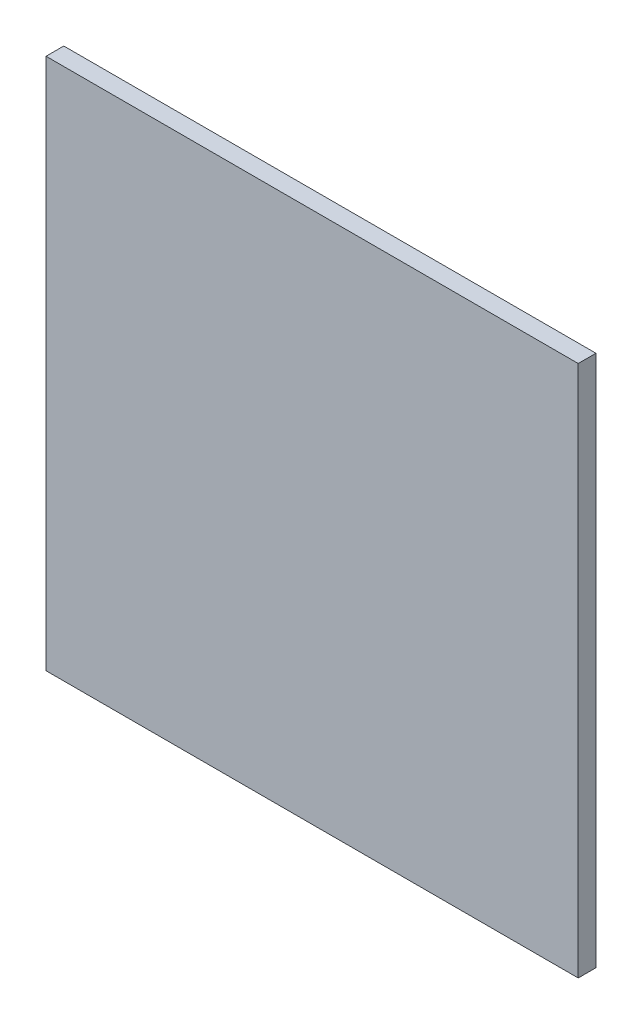
SolidWorks part; units mm, degrees
ref_plane "Спереди" through (0, 0, 0) normal (0, 0, 1) x (1, 0, 0)
ref_plane "Сверху" through (0, 0, 0) normal (0, 1, 0) x (1, 0, 0)
ref_plane "Справа" through (0, 0, 0) normal (1, 0, 0) x (0, 0, -1)
sketch "Эскиз1" plane through (0, 0, 0) normal (0, 0, 1) x (1, 0, 0)
  line L5 (30, 30) -> (-30, 30)
  line L6 (30, 30) -> (30, -30)
  line L7 (30, -30) -> (-30, -30)
  line L8 (-30, 30) -> (-30, -30)
  line L9 (30, 30) -> (-30, -30) construction
  line L10 (30, -30) -> (-30, 30) construction
  point P0 (0, 0)
  point P1 (0, 0)
extrude "Бобышка-Вытянуть1" add sketch "Эскиз1" along normal blind 2
sketch "Острова" plane through (0, 0, 2) normal (0, 0, 1) x (1, 0, 0)
  circle A0 centre (0, 0) radius 3.4
  circle A27 centre (-14.6858, 0.6384) radius 0.5
sketch "Внешний контур" plane through (0, 0, 2) normal (0, 0, 1) x (1, 0, 0)
  circle A0 centre (0, 0) radius 18.1
sketch "малое" plane through (0, 0, 2) normal (0, 0, 1) x (1, 0, 0)
  circle A0 centre (-14.6858, 0.6384) radius 3.1837
sketch "Платина" plane through (0, 0, 2) normal (0, 0, 1) x (1, 0, 0)
  line L0 (-16.46, -2.2319) -> (-17.6833, -3.1445)
  line L1 (-15.9169, 4.5359) -> (-17.3141, 3.4937)
  line L2 (-9.9961, -0.621) -> (-8.9843, -0.8481)
  line L3 (-8.1465, 12.0191) -> (-11.9685, 4.612)
  circle A0 centre (15.8604, -7.3958) radius 0.3
  circle A1 centre (-15.8604, -7.3958) radius 0.3
  circle A2 centre (-15.1554, -8.75) radius 0.2
  circle A3 centre (15.1554, -8.75) radius 0.2
  circle A4 centre (-15.1554, 8.75) radius 0.2
  circle A5 centre (-4.5293, 16.9037) radius 0.3
  circle A6 centre (15.1554, 8.75) radius 0.2
  circle A7 centre (13.0577, 8.3514) radius 0.405
  circle A8 centre (11.8737, 9.9632) radius 0.75
  circle A9 centre (-11.8737, -9.9632) radius 0.75
  circle A10 centre (9.7987, -9.2863) radius 0.6
  circle A11 centre (-9.7987, -9.2863) radius 0.6
  circle A12 centre (-13.0577, -8.3514) radius 0.405
  circle A13 centre (-10.9359, 0.1356) radius 0.4
  circle A14 centre (-9.1125, 6.4014) radius 0.3
  circle A15 centre (7.4113, 9.6267) radius 0.3
  circle A16 centre (10.6793, 8.251) radius 0.4
  circle A17 centre (-3.3737, 15.282) radius 0.2
  circle A18 centre (-6.2277, 14.3575) radius 0.2
  circle A19 centre (-14.6858, 0.6384) radius 1.5
  circle A20 centre (1.976, -9.4455) radius 0.4
  circle A21 centre (-3.9878, -8.7875) radius 0.4
  circle A22 centre (3.8165, -8.769) radius 0.4
  circle A23 centre (0, -8.769) radius 0.3
  circle A24 centre (-6.0695, 1.9805) radius 0.3
  circle A25 centre (-5.5825, 3.7945) radius 0.4
  circle A26 centre (14.6858, 0.6384) radius 0.5
  circle A27 centre (-14.6858, 0.6384) radius 0.5
  circle A28 centre (-11.8737, -9.9632) radius 0.425
  circle A29 centre (11.8737, 9.9632) radius 0.425
  circle A30 centre (0, 9.5) radius 1
  circle A31 centre (0, 9.5) radius 0.5
  circle A32 centre (7.8326, 2.0642) radius 1
  circle A33 centre (7.8326, 2.0642) radius 0.5
  arc A34 (-17.7579, -3.2341) -> (18.0241, 0.9669) centre (0, 0) ccw
  arc A35 (16.9226, 6.2793) -> (-17.6898, 3.5877) centre (0, 0) ccw
  arc A36 (16.9162, 6.4383) -> (18.0815, 0.8185) centre (0, 0) ccw
  arc A37 (-16.7505, -2.9017) -> (16.9984, -0.2297) centre (0, 0) ccw
  arc A38 (17.0093, -0.1602) -> (16.9984, -0.2297) centre (17.2484, -0.2331) ccw
  arc A39 (6.1802, -9.134) -> (17.1591, 0.3729) centre (4.7934, 3.5604) ccw
  arc A40 (17.7356, 1.0379) -> (17.1591, 0.3729) centre (18.1152, 0.1265) ccw
  arc A41 (-16.7505, -2.9017) -> (-17.1463, -2.7439) centre (-16.9969, -2.9443) ccw
  arc A42 (-17.6833, -3.1445) -> (-17.7579, -3.2341) centre (-17.5338, -3.3449) ccw
  arc A43 (18.0241, 0.9669) -> (17.7356, 1.0379) centre (17.8317, 0.8072) ccw
  arc A44 (15.7254, 6.4584) -> (15.9042, 6.3089) centre (15.9567, 6.5534) ccw
  arc A45 (-16.5688, 4.0497) -> (-16.4759, 4.1885) centre (-16.7182, 4.25) ccw
  arc A46 (15.7254, 6.4584) -> (-16.4759, 4.1885) centre (0, 0) ccw
  arc A47 (16.6001, 6.1133) -> (13.2947, 6.2691) centre (14.6858, 0.6384) ccw
  arc A48 (16.6001, 6.1133) -> (16.9226, 6.2793) centre (16.6826, 6.3493) ccw
  arc A49 (-17.6898, 3.5877) -> (-17.3141, 3.4937) centre (-17.4636, 3.694) ccw
  arc A50 (-1.8822, 15.2674) -> (-3.5714, 16.1089) centre (-3.2467, 14.6444) ccw
  arc A51 (-3.5714, 16.1089) -> (-15.8266, 4.6656) centre (0, 0) ccw
  arc A52 (-15.9169, 4.5359) -> (-15.8266, 4.6656) centre (-16.0664, 4.7363) ccw
  arc A53 (13.0105, 6.4014) -> (13.2947, 6.2691) centre (13.2348, 6.5118) ccw
  arc A54 (13.0105, 6.4014) -> (3.7718, 14.0008) centre (0, 0) ccw
  arc A55 (3.6796, 14.0479) -> (3.7718, 14.0008) centre (3.8368, 14.2422) ccw
  arc A56 (-1.8822, 15.2674) -> (-1.587, 15.1306) centre (-1.6548, 15.3713) ccw
  arc A57 (6.1802, -9.134) -> (6.0694, -9.174) centre (6.2073, -9.3825) ccw
  arc A58 (-16.0859, -2.3226) -> (-16.46, -2.2319) centre (-16.3105, -2.4323) ccw
  arc A59 (-16.0859, -2.3226) -> (-6.1386, -9.1642) centre (-5.0527, 3.0669) ccw
  arc A60 (-6.0238, -9.204) -> (-6.1386, -9.1642) centre (-6.1607, -9.4132) ccw
  arc A61 (-10.9038, -1.4518) -> (6.0694, -9.174) centre (0, 0) ccw
  arc A62 (-8.6376, 11.0178) -> (-8.7055, 10.9357) centre (-8.4833, 10.8211) ccw
  arc A63 (-5.2609, 12.9739) -> (-8.6376, 11.0178) centre (0, 0) ccw
  arc A64 (-5.412, 6.8118) -> (-5.3394, 7.1097) centre (-5.5675, 7.0075) ccw
  arc A65 (-5.412, 6.8118) -> (-8.6802, -0.5873) centre (0, 0) ccw
  arc A66 (-8.9843, -0.8481) -> (-8.6802, -0.5873) centre (-8.9296, -0.6042) ccw
  arc A67 (-9.9961, -0.621) -> (-10.9038, -1.4518) centre (-10.1603, -1.3528) ccw
  arc A68 (-10.9454, -0.8345) -> (-10.6639, -0.797) centre (-10.8318, -0.6118) ccw
  arc A69 (-12.5553, 0.2584) -> (-10.9454, -0.8345) centre (-7.3887, 6.137) ccw
  arc A70 (-12.6113, 0.5629) -> (-12.5553, 0.2584) centre (-12.3902, 0.4462) ccw
  arc A71 (-12.6113, 0.5629) -> (-11.9927, 4.455) centre (-18.0219, 3.4181) ccw
  arc A72 (-11.9685, 4.612) -> (-11.9927, 4.455) centre (-11.7463, 4.4973) ccw
  arc A73 (-4.9552, 12.6094) -> (-5.2609, 12.9739) centre (-5.167, 12.7422) ccw
  arc A74 (12.7242, 6.953) -> (11.2236, 7.1836) centre (11.8858, 6.4949) ccw
  arc A75 (5.6594, 8.019) -> (5.9792, 7.7182) centre (5.9013, 7.9557) ccw
  arc A76 (10.9206, 7.1501) -> (11.2236, 7.1836) centre (11.0503, 7.3638) ccw
  arc A77 (-8.1465, 12.0191) -> (-9.6966, 13.3501) centre (-9.0796, 12.5005) ccw
  arc A78 (1.62, 2.9892) -> (2.8829, -1.8025) centre (0, 0) ccw
  arc A79 (3.207, -2.8598) -> (2.2208, -2.5745) centre (2.621, -3.0384) ccw
  arc A80 (3.207, -2.8598) -> (4.6866, -5.996) centre (14.6858, 0.6384) ccw
  arc A81 (4.6517, -7.2936) -> (4.6866, -5.996) centre (3.7461, -6.62) ccw
  arc A82 (4.6517, -7.2936) -> (5.5116, -8.8888) centre (5.454, -7.8905) ccw
  arc A83 (5.5116, -8.8888) -> (9.3798, -8.0354) centre (4.7934, 3.5604) ccw
  arc A84 (9.3798, -8.0354) -> (9.603, -6.2989) centre (9.012, -7.1055) ccw
  arc A85 (8.1607, -4.9637) -> (9.603, -6.2989) centre (14.6858, 0.6384) ccw
  arc A86 (8.5933, -3.837) -> (8.1607, -4.9637) centre (8.681, -4.517) ccw
  arc A87 (-4.8992, 6.0148) -> (-3.5098, 4.6184) centre (-4.0817, 5.4388) ccw
  arc A88 (2.09, 3.6214) -> (1.7729, 3.9251) centre (1.8487, 3.6869) ccw
  arc A89 (-4.8992, 6.0148) -> (-4.8944, 6.2957) centre (-5.1035, 6.1588) ccw
  arc A90 (-3.2289, 4.6218) -> (-3.5098, 4.6184) centre (-3.3669, 4.4133) ccw
  arc A91 (1.62, 2.9892) -> (1.9849, 3.1629) centre (1.7392, 3.209) ccw
  arc A92 (13.6153, -0.4124) -> (13.2109, -0.4806) centre (13.4369, -0.5875) ccw
  arc A93 (13.7796, 2.2527) -> (14.1232, 2.0289) centre (14.0295, 2.2606) ccw
  arc A94 (2.09, 3.6214) -> (1.9849, 3.1629) centre (7.8326, 2.0642) ccw
  arc A95 (13.6153, -0.4124) -> (14.1232, 2.0289) centre (14.6858, 0.6384) ccw
  arc A96 (3.2859, -1.7738) -> (5.9792, 7.7182) centre (7.8326, 2.0642) ccw
  arc A97 (5.6594, 8.019) -> (1.7729, 3.9251) centre (0, 9.5) ccw
  arc A98 (18.0815, 0.8185) -> (16.9162, 6.4383) centre (0, 0) ccw
  arc A99 (3.2859, -1.7738) -> (2.8829, -1.8025) centre (3.0948, -1.935) ccw
  arc A100 (2.8829, -1.8025) -> (1.62, 2.9892) centre (0, 0) ccw
  spline S0 degree 3 poles (-17.7794, -3.3917) (-17.7902, -3.335) (-17.7798, -3.2784) (-17.7579, -3.2341) knots 0 0 0 0 1 1 1 1
  spline S1 degree 3 poles (18.0241, 0.9669) (18.0557, 0.9288) (18.0789, 0.8762) (18.0815, 0.8185) knots 0 0 0 0 1 1 1 1
  spline S2 degree 3 poles (-17.6898, 3.5877) (-17.7109, 3.6325) (-17.7201, 3.6892) (-17.7082, 3.7458) knots 0 0 0 0 1 1 1 1
  spline S3 degree 3 poles (16.9162, 6.4383) (16.9368, 6.3843) (16.9364, 6.3267) (16.9226, 6.2793) knots 0 0 0 0 1 1 1 1
sketch "Задник" plane through (0, 0, 2) normal (0, 0, 1) x (1, 0, 0)
  circle A1 centre (-13.8089, 0.5381) radius 1.48
  circle A2 centre (-17.7726, -1.3915) radius 1.48
  circle A3 centre (-17.8207, 0.4738) radius 1.48
  circle A4 centre (-17.6735, 2.334) radius 1.48
  circle A5 centre (-17.3327, 4.1686) radius 1.48
  circle A6 centre (-16.802, 5.9575) radius 1.48
  circle A7 centre (-16.0873, 7.6812) radius 1.48
  circle A8 centre (-15.1962, 9.3207) radius 1.48
  circle A9 centre (-14.1387, 10.858) radius 1.48
  circle A10 centre (-12.9263, 12.2765) radius 1.48
  circle A11 centre (-11.5722, 13.5604) radius 1.48
  circle A12 centre (-10.0914, 14.6957) radius 1.48
  circle A13 centre (-8.5, 15.67) radius 1.48
  circle A14 centre (-6.8155, 16.4727) radius 1.48
  circle A15 centre (-5.0563, 17.0949) radius 1.48
  circle A16 centre (-3.2417, 17.5297) radius 1.48
  circle A17 centre (-1.3915, 17.7726) radius 1.48
  circle A18 centre (0.4738, 17.8207) radius 1.48
  circle A19 centre (2.334, 17.6735) radius 1.48
  circle A20 centre (4.1686, 17.3327) radius 1.48
  circle A21 centre (5.9575, 16.802) radius 1.48
  circle A22 centre (7.6812, 16.0873) radius 1.48
  circle A23 centre (9.3207, 15.1962) radius 1.48
  circle A24 centre (10.858, 14.1387) radius 1.48
  circle A25 centre (12.2765, 12.9263) radius 1.48
  circle A26 centre (13.5604, 11.5722) radius 1.48
  circle A27 centre (14.6957, 10.0914) radius 1.48
  circle A28 centre (15.67, 8.5) radius 1.48
  circle A29 centre (16.4727, 6.8155) radius 1.48
  circle A30 centre (17.0949, 5.0563) radius 1.48
  circle A31 centre (17.5297, 3.2417) radius 1.48
  circle A32 centre (17.7726, 1.3915) radius 1.48
  circle A33 centre (17.8207, -0.4738) radius 1.48
  circle A34 centre (17.6735, -2.334) radius 1.48
  circle A35 centre (17.3327, -4.1686) radius 1.48
  circle A36 centre (16.802, -5.9575) radius 1.48
  circle A37 centre (16.0873, -7.6812) radius 1.48
  circle A38 centre (15.1962, -9.3207) radius 1.48
  circle A39 centre (14.1387, -10.858) radius 1.48
  circle A40 centre (12.9263, -12.2765) radius 1.48
  circle A41 centre (11.5722, -13.5604) radius 1.48
  circle A42 centre (10.0914, -14.6957) radius 1.48
  circle A43 centre (8.5, -15.67) radius 1.48
  circle A44 centre (6.8155, -16.4727) radius 1.48
  circle A45 centre (5.0563, -17.0949) radius 1.48
  circle A46 centre (3.2417, -17.5297) radius 1.48
  circle A47 centre (1.3915, -17.7726) radius 1.48
  circle A48 centre (-0.4738, -17.8207) radius 1.48
  circle A49 centre (-2.334, -17.6735) radius 1.48
  circle A50 centre (-4.1686, -17.3327) radius 1.48
  circle A51 centre (-5.9575, -16.802) radius 1.48
  circle A52 centre (-7.6812, -16.0873) radius 1.48
  circle A53 centre (-9.3207, -15.1962) radius 1.48
  circle A54 centre (-10.858, -14.1387) radius 1.48
  circle A55 centre (-12.2765, -12.9263) radius 1.48
  circle A56 centre (-13.5604, -11.5722) radius 1.48
  circle A57 centre (-14.6957, -10.0914) radius 1.48
  circle A58 centre (-15.67, -8.5) radius 1.48
  circle A59 centre (-16.4727, -6.8155) radius 1.48
  circle A60 centre (-17.0949, -5.0563) radius 1.48
  circle A61 centre (-17.5297, -3.2417) radius 1.48
  circle A62 centre (-15.7682, -0.6037) radius 1.48
  circle A63 centre (-15.7343, 1.1976) radius 1.48
  circle A64 centre (-15.4952, 2.9834) radius 1.48
  circle A65 centre (-15.0541, 4.7303) radius 1.48
  circle A66 centre (-14.4168, 6.4155) radius 1.48
  circle A67 centre (-13.5915, 8.0171) radius 1.48
  circle A68 centre (-12.589, 9.5141) radius 1.48
  circle A69 centre (-11.4224, 10.8871) radius 1.48
  circle A70 centre (-10.1069, 12.1182) radius 1.48
  circle A71 centre (-8.6597, 13.1913) radius 1.48
  circle A72 centre (-7.0995, 14.0925) radius 1.48
  circle A73 centre (-5.4468, 14.8099) radius 1.48
  circle A74 centre (-3.7231, 15.3343) radius 1.48
  circle A75 centre (-1.9509, 15.6587) radius 1.48
  circle A76 centre (-0.1532, 15.779) radius 1.48
  circle A77 centre (1.6465, 15.6937) radius 1.48
  circle A78 centre (3.4247, 15.4037) radius 1.48
  circle A79 centre (5.1582, 14.9129) radius 1.48
  circle A80 centre (6.8246, 14.2277) radius 1.48
  circle A81 centre (8.4019, 13.357) radius 1.48
  circle A82 centre (9.8697, 12.3122) radius 1.48
  circle A83 centre (11.2089, 11.1069) radius 1.48
  circle A84 centre (12.4019, 9.7568) radius 1.48
  circle A85 centre (13.4333, 8.2795) radius 1.48
  circle A86 centre (14.2895, 6.6942) radius 1.48
  circle A87 centre (14.9594, 5.0217) radius 1.48
  circle A88 centre (15.4343, 3.2837) radius 1.48
  circle A89 centre (15.7081, 1.5029) radius 1.48
  circle A90 centre (15.777, -0.2974) radius 1.48
  circle A91 centre (15.6402, -2.0939) radius 1.48
  circle A92 centre (15.2996, -3.8631) radius 1.48
  circle A93 centre (14.7595, -5.582) radius 1.48
  circle A94 centre (14.027, -7.2281) radius 1.48
  circle A95 centre (13.1116, -8.7799) radius 1.48
  circle A96 centre (12.0253, -10.2173) radius 1.48
  circle A97 centre (10.7823, -11.5215) radius 1.48
  circle A98 centre (9.3986, -12.6755) radius 1.48
  circle A99 centre (7.8925, -13.6642) radius 1.48
  circle A100 centre (6.2834, -14.4748) radius 1.48
  circle A101 centre (4.5925, -15.0967) radius 1.48
  circle A102 centre (2.8416, -15.5218) radius 1.48
  circle A103 centre (1.0538, -15.7446) radius 1.48
  circle A104 centre (-0.7478, -15.7621) radius 1.48
  circle A105 centre (-2.5397, -15.5741) radius 1.48
  circle A106 centre (-4.2985, -15.1831) radius 1.48
  circle A107 centre (-6.0012, -14.5941) radius 1.48
  circle A108 centre (-7.6257, -13.8149) radius 1.48
  circle A109 centre (-9.1507, -12.8556) radius 1.48
  circle A110 centre (-10.5565, -11.7287) radius 1.48
  circle A111 centre (-11.8247, -10.4489) radius 1.48
  circle A112 centre (-12.9387, -9.0328) radius 1.48
  circle A113 centre (-13.884, -7.4991) radius 1.48
  circle A114 centre (-14.6483, -5.8675) radius 1.48
  circle A115 centre (-15.2217, -4.1595) radius 1.48
  circle A116 centre (-15.5966, -2.3972) radius 1.48
  circle A117 centre (-13.7574, -1.3073) radius 1.48
  circle A118 centre (-13.614, 2.3738) radius 1.48
  circle A119 centre (-13.1761, 4.1672) radius 1.48
  circle A120 centre (-12.5031, 5.8862) radius 1.48
  circle A121 centre (-11.607, 7.5002) radius 1.48
  circle A122 centre (-10.5037, 8.9803) radius 1.48
  circle A123 centre (-9.2131, 10.3002) radius 1.48
  circle A124 centre (-7.758, 11.4363) radius 1.48
  circle A125 centre (-6.1644, 12.3683) radius 1.48
  circle A126 centre (-4.4609, 13.0796) radius 1.48
  circle A127 centre (-2.6778, 13.5574) radius 1.48
  circle A128 centre (-0.8469, 13.7934) radius 1.48
  circle A129 centre (0.9992, 13.7832) radius 1.48
  circle A130 centre (2.8274, 13.527) radius 1.48
  circle A131 centre (4.6051, 13.0295) radius 1.48
  circle A132 centre (6.3007, 12.2994) radius 1.48
  circle A133 centre (7.8838, 11.3499) radius 1.48
  circle A134 centre (9.3263, 10.1978) radius 1.48
  circle A135 centre (10.6023, 8.8637) radius 1.48
  circle A136 centre (11.6891, 7.3715) radius 1.48
  circle A137 centre (12.5674, 5.7477) radius 1.48
  circle A138 centre (13.2213, 4.0214) radius 1.48
  circle A139 centre (13.6394, 2.2233) radius 1.48
  circle A140 centre (13.814, 0.3855) radius 1.48
  circle A141 centre (13.7421, -1.4592) radius 1.48
  circle A142 centre (13.425, -3.2778) radius 1.48
  circle A143 centre (12.8683, -5.0379) radius 1.48
  circle A144 centre (12.082, -6.7082) radius 1.48
  circle A145 centre (11.0801, -8.2587) radius 1.48
  circle A146 centre (9.8805, -9.6618) radius 1.48
  circle A147 centre (8.5045, -10.8926) radius 1.48
  circle A148 centre (6.9768, -11.9289) radius 1.48
  circle A149 centre (5.3246, -12.7524) radius 1.48
  circle A150 centre (3.5773, -13.3483) radius 1.48
  circle A151 centre (1.7663, -13.706) radius 1.48
  circle A152 centre (-0.0763, -13.8192) radius 1.48
  circle A153 centre (-1.9176, -13.6857) radius 1.48
  circle A154 centre (-3.7246, -13.308) radius 1.48
  circle A155 centre (-5.4651, -12.6928) radius 1.48
  circle A156 centre (-7.1082, -11.8511) radius 1.48
  circle A157 centre (-8.6243, -10.798) radius 1.48
  circle A158 centre (-9.9866, -9.5521) radius 1.48
  circle A159 centre (-11.1707, -8.1358) radius 1.48
  circle A160 centre (-12.1554, -6.5743) radius 1.48
  circle A161 centre (-12.9232, -4.8955) radius 1.48
  circle A162 centre (-13.4604, -3.1293) radius 1.48
  circle A163 centre (-11.4788, 2.7918) radius 1.48
  circle A164 centre (-10.8627, 4.6431) radius 1.48
  circle A165 centre (-9.9503, 6.3677) radius 1.48
  circle A166 centre (-8.7665, 7.9186) radius 1.48
  circle A167 centre (-7.3436, 9.2536) radius 1.48
  circle A168 centre (-5.7204, 10.3361) radius 1.48
  circle A169 centre (-3.9411, 11.1366) radius 1.48
  circle A170 centre (-2.0543, 11.6334) radius 1.48
  circle A171 centre (-0.1115, 11.8129) radius 1.48
  circle A172 centre (1.8344, 11.6701) radius 1.48
  circle A173 centre (3.7302, 11.209) radius 1.48
  circle A174 centre (5.5243, 10.4422) radius 1.48
  circle A175 centre (7.1677, 9.3905) radius 1.48
  circle A176 centre (8.6155, 8.0827) radius 1.48
  circle A177 centre (9.8284, 6.5544) radius 1.48
  circle A178 centre (10.7731, 4.8473) radius 1.48
  circle A179 centre (11.424, 3.008) radius 1.48
  circle A180 centre (11.7633, 1.0866) radius 1.48
  circle A181 centre (11.7817, -0.8644) radius 1.48
  circle A182 centre (11.4788, -2.7918) radius 1.48
  circle A183 centre (10.8627, -4.6431) radius 1.48
  circle A184 centre (9.9503, -6.3677) radius 1.48
  circle A185 centre (8.7665, -7.9186) radius 1.48
  circle A186 centre (7.3436, -9.2536) radius 1.48
  circle A187 centre (5.7204, -10.3361) radius 1.48
  circle A188 centre (3.9411, -11.1366) radius 1.48
  circle A189 centre (2.0543, -11.6334) radius 1.48
  circle A190 centre (0.1115, -11.8129) radius 1.48
  circle A191 centre (-1.8344, -11.6701) radius 1.48
  circle A192 centre (-3.7302, -11.209) radius 1.48
  circle A193 centre (-5.5243, -10.4422) radius 1.48
  circle A194 centre (-7.1677, -9.3905) radius 1.48
  circle A195 centre (-8.6155, -8.0827) radius 1.48
  circle A196 centre (-9.8284, -6.5544) radius 1.48
  circle A197 centre (-10.7731, -4.8473) radius 1.48
  circle A198 centre (-11.424, -3.008) radius 1.48
  circle A199 centre (-11.7633, -1.0866) radius 1.48
  circle A200 centre (-11.7817, 0.8644) radius 1.48
  circle A201 centre (-9.4232, 3.0168) radius 1.48
  circle A202 centre (-8.623, 4.8519) radius 1.48
  circle A203 centre (-7.4698, 6.4884) radius 1.48
  circle A204 centre (-6.0108, 7.8592) radius 1.48
  circle A205 centre (-4.3057, 8.9083) radius 1.48
  circle A206 centre (-2.4243, 9.5927) radius 1.48
  circle A207 centre (-0.4437, 9.8843) radius 1.48
  circle A208 centre (1.5551, 9.7713) radius 1.48
  circle A209 centre (3.4902, 9.2583) radius 1.48
  circle A210 centre (5.2824, 8.3662) radius 1.48
  circle A211 centre (6.8584, 7.1316) radius 1.48
  circle A212 centre (8.1536, 5.605) radius 1.48
  circle A213 centre (9.1149, 3.849) radius 1.48
  circle A214 centre (9.7032, 1.9354) radius 1.48
  circle A215 centre (9.8941, -0.0575) radius 1.48
  circle A216 centre (9.68, -2.048) radius 1.48
  circle A217 centre (9.0696, -3.9546) radius 1.48
  circle A218 centre (8.0879, -5.6994) radius 1.48
  circle A219 centre (6.7751, -7.2108) radius 1.48
  circle A220 centre (5.1849, -8.427) radius 1.48
  circle A221 centre (3.3824, -9.2982) radius 1.48
  circle A222 centre (1.4414, -9.7887) radius 1.48
  circle A223 centre (-0.5585, -9.8785) radius 1.48
  circle A224 centre (-2.5356, -9.5639) radius 1.48
  circle A225 centre (-4.4089, -8.8577) radius 1.48
  circle A226 centre (-6.1017, -7.7888) radius 1.48
  circle A227 centre (-7.5447, -6.4011) radius 1.48
  circle A228 centre (-8.6788, -4.7514) radius 1.48
  circle A229 centre (-9.4576, -2.9071) radius 1.48
  circle A230 centre (-9.8492, -0.9438) radius 1.48
  circle A231 centre (-9.8375, 1.0582) radius 1.48
  circle A232 centre (-6.6412, 4.5323) radius 1.48
  circle A233 centre (-5.3054, 6.0415) radius 1.48
  circle A234 centre (-3.6362, 7.1711) radius 1.48
  circle A235 centre (-1.7386, 7.8501) radius 1.48
  circle A236 centre (0.2682, 8.0359) radius 1.48
  circle A237 centre (2.2583, 7.7167) radius 1.48
  circle A238 centre (4.1064, 6.9127) radius 1.48
  circle A239 centre (5.6965, 5.6743) radius 1.48
  circle A240 centre (6.9287, 4.0794) radius 1.48
  circle A241 centre (7.7255, 2.2281) radius 1.48
  circle A242 centre (8.0369, 0.2369) radius 1.48
  circle A243 centre (7.8433, -1.7693) radius 1.48
  circle A244 centre (7.1569, -3.6642) radius 1.48
  circle A245 centre (6.0208, -5.329) radius 1.48
  circle A246 centre (4.5064, -6.6588) radius 1.48
  circle A247 centre (2.7088, -7.5703) radius 1.48
  circle A248 centre (0.741, -8.0061) radius 1.48
  circle A249 centre (-1.2733, -7.9389) radius 1.48
  circle A250 centre (-3.2076, -7.3728) radius 1.48
  circle A251 centre (-4.9404, -6.3435) radius 1.48
  circle A252 centre (-6.3627, -4.9156) radius 1.48
  circle A253 centre (-7.3853, -3.1788) radius 1.48
  circle A254 centre (-7.9438, -1.2423) radius 1.48
  circle A255 centre (-8.0032, 0.7723) radius 1.48
  circle A256 centre (-7.5597, 2.7383) radius 1.48
  circle A257 centre (-5.8236, 1.2841) radius 1.48
  circle A258 centre (-5.0912, 3.1054) radius 1.48
  circle A259 centre (-3.807, 4.5903) radius 1.48
  circle A260 centre (-2.1103, 5.5777) radius 1.48
  circle A261 centre (-0.1848, 5.9607) radius 1.48
  circle A262 centre (1.7606, 5.6977) radius 1.48
  circle A263 centre (3.5152, 4.8173) radius 1.48
  circle A264 centre (4.889, 3.4149) radius 1.48
  circle A265 centre (5.7329, 1.6424) radius 1.48
  circle A266 centre (5.9556, -0.308) radius 1.48
  circle A267 centre (5.5329, -2.2251) radius 1.48
  circle A268 centre (4.5106, -3.901) radius 1.48
  circle A269 centre (2.9995, -5.1543) radius 1.48
  circle A270 centre (1.1634, -5.8489) radius 1.48
  circle A271 centre (-0.7988, -5.9098) radius 1.48
  circle A272 centre (-2.6744, -5.3302) radius 1.48
  circle A273 centre (-4.2602, -4.173) radius 1.48
  circle A274 centre (-5.3844, -2.5636) radius 1.48
  circle A275 centre (-5.925, -0.6764) radius 1.48
  circle A276 centre (-2.9274, 2.4949) radius 1.48
  circle A277 centre (-1.2877, 3.6244) radius 1.48
  circle A278 centre (0.697, 3.7826) radius 1.48
  circle A279 centre (2.4949, 2.9274) radius 1.48
  circle A280 centre (3.6244, 1.2877) radius 1.48
  circle A281 centre (3.7826, -0.697) radius 1.48
  circle A282 centre (2.9274, -2.4949) radius 1.48
  circle A283 centre (1.2877, -3.6244) radius 1.48
  circle A284 centre (-0.697, -3.7826) radius 1.48
  circle A285 centre (-2.4949, -2.9274) radius 1.48
  circle A286 centre (-3.6244, -1.2877) radius 1.48
  circle A287 centre (-3.7826, 0.697) radius 1.48
  point P123 (0, 0)
  point P234 (0, 0)
  point P329 (0, 0)
  point P406 (0, 0)
  point P469 (0, 0)
  point P520 (0, 0)
  point P559 (0, 0)
  point P584 (0, 0)
  dimension "D1" = 60
  dimension "D2" = 55
  dimension "D3" = 47
  dimension "D4" = 38
  dimension "D5" = 31
  dimension "D6" = 25
  dimension "D7" = 19
  dimension "D8" = 12
sketch "1" plane through (0, 0, 2) normal (0, 0, 1) x (1, 0, 0)
  circle A232 centre (-1.1322, 14.1902) radius 1
  circle A233 centre (0.0698, 14.3244) radius 1
  circle A234 centre (1.2673, 14.1555) radius 1
  circle A235 centre (2.3853, 13.694) radius 1
  circle A236 centre (3.3534, 12.9691) radius 1
  circle A237 centre (4.1107, 12.0261) radius 1
  circle A238 centre (4.6098, 10.9245) radius 1
  circle A239 centre (4.8192, 9.7333) radius 1
  circle A240 centre (4.7258, 8.5275) radius 1
  circle A241 centre (4.3355, 7.3828) radius 1
  circle A242 centre (3.6728, 6.3711) radius 1
  circle A243 centre (2.7792, 5.556) radius 1
  circle A244 centre (1.7111, 4.9887) radius 1
  circle A245 centre (0.5354, 4.7049) radius 1
  circle A246 centre (-0.6739, 4.7224) radius 1
  circle A247 centre (-1.8408, 5.0401) radius 1
  circle A248 centre (-2.8921, 5.638) radius 1
  circle A249 centre (-3.7617, 6.4786) radius 1
  circle A250 centre (-4.3949, 7.509) radius 1
  circle A251 centre (-4.752, 8.6645) radius 1
  circle A252 centre (-4.8105, 9.8726) radius 1
  circle A253 centre (-4.5667, 11.0572) radius 1
  circle A254 centre (-4.036, 12.1439) radius 1
  circle A255 centre (-3.2516, 13.0646) radius 1
  circle A256 centre (-2.263, 13.7612) radius 1
  circle A257 centre (-0.4876, 13.2007) radius 1
  circle A258 centre (0.8076, 13.1443) radius 1
  circle A259 centre (2.0053, 12.6483) radius 1
  circle A260 centre (2.9611, 11.7726) radius 1
  circle A261 centre (3.5598, 10.6228) radius 1
  circle A262 centre (3.7292, 9.3375) radius 1
  circle A263 centre (3.4487, 8.0719) radius 1
  circle A264 centre (2.7523, 6.9785) radius 1
  circle A265 centre (1.7239, 6.1892) radius 1
  circle A266 centre (0.4876, 5.7993) radius 1
  circle A267 centre (-0.8076, 5.8557) radius 1
  circle A268 centre (-2.0053, 6.3517) radius 1
  circle A269 centre (-2.9611, 7.2274) radius 1
  circle A270 centre (-3.5598, 8.3772) radius 1
  circle A271 centre (-3.7292, 9.6625) radius 1
  circle A272 centre (-3.4487, 10.9281) radius 1
  circle A273 centre (-2.7523, 12.0215) radius 1
  circle A274 centre (-1.7239, 12.8108) radius 1
  circle A275 centre (0.1419, 12.2057) radius 1
  circle A276 centre (1.3831, 11.8298) radius 1
  circle A277 centre (2.3074, 10.9202) radius 1
  circle A278 centre (2.7031, 9.6852) radius 1
  circle A279 centre (2.4796, 8.4078) radius 1
  circle A280 centre (1.688, 7.3806) radius 1
  circle A281 centre (0.5097, 6.8389) radius 1
  circle A282 centre (-0.7853, 6.9069) radius 1
  circle A283 centre (-1.9005, 7.5689) radius 1
  circle A284 centre (-2.5802, 8.6733) radius 1
  circle A285 centre (-2.6689, 9.9671) radius 1
  circle A286 centre (-2.1461, 11.1538) radius 1
  circle A287 centre (-1.1317, 11.9618) radius 1
  circle A288 centre (-0.3151, 11.181) radius 1
  circle A289 centre (0.9659, 10.9114) radius 1
  circle A290 centre (1.681, 9.8151) radius 1
  circle A291 centre (1.4114, 8.5341) radius 1
  circle A292 centre (0.3151, 7.819) radius 1
  circle A293 centre (-0.9659, 8.0886) radius 1
  circle A294 centre (-1.681, 9.1849) radius 1
  circle A295 centre (-1.4114, 10.4659) radius 1
  point P53 (0, 9.5)
  point P89 (0, 9.5)
  point P117 (0, 9.5)
  point P134 (0, 9.5)
  dimension "D1" = 25
  dimension "D2" = 18
  dimension "D3" = 13
sketch "2" plane through (0, 0, 2) normal (0, 0, 1) x (1, 0, 0)
  circle A0 centre (6.6966, 6.7313) radius 1
  circle A1 centre (7.8986, 6.8655) radius 1
  circle A2 centre (9.0961, 6.6966) radius 1
  circle A3 centre (10.2141, 6.2352) radius 1
  circle A4 centre (11.1822, 5.5102) radius 1
  circle A5 centre (11.9395, 4.5673) radius 1
  circle A6 centre (12.4386, 3.4656) radius 1
  circle A7 centre (12.648, 2.2744) radius 1
  circle A8 centre (12.5546, 1.0686) radius 1
  circle A9 centre (12.1643, -0.0761) radius 1
  circle A10 centre (11.5016, -1.0878) radius 1
  circle A11 centre (10.6081, -1.9029) radius 1
  circle A12 centre (9.5399, -2.4701) radius 1
  circle A13 centre (8.3642, -2.7539) radius 1
  circle A14 centre (7.1549, -2.7364) radius 1
  circle A15 centre (5.988, -2.4188) radius 1
  circle A16 centre (4.9367, -1.8208) radius 1
  circle A17 centre (4.0671, -0.9803) radius 1
  circle A21 centre (3.2621, 3.5983) radius 1
  circle A22 centre (3.7928, 4.6851) radius 1
  circle A23 centre (4.5772, 5.6057) radius 1
  circle A24 centre (5.5658, 6.3024) radius 1
  circle A25 centre (7.3412, 5.7418) radius 1
  circle A26 centre (8.6364, 5.6854) radius 1
  circle A27 centre (9.8341, 5.1895) radius 1
  circle A28 centre (10.7899, 4.3137) radius 1
  circle A29 centre (11.3886, 3.1639) radius 1
  circle A30 centre (11.558, 1.8787) radius 1
  circle A31 centre (11.2775, 0.613) radius 1
  circle A32 centre (10.5811, -0.4804) radius 1
  circle A33 centre (9.5527, -1.2696) radius 1
  circle A34 centre (8.3164, -1.6596) radius 1
  circle A35 centre (7.0213, -1.6031) radius 1
  circle A36 centre (5.8235, -1.1072) radius 1
  circle A37 centre (4.8677, -0.2315) radius 1
  circle A38 centre (4.269, 0.9184) radius 1
  circle A39 centre (4.0996, 2.2036) radius 1
  circle A40 centre (4.3801, 3.4692) radius 1
  circle A41 centre (5.0765, 4.5626) radius 1
  circle A42 centre (6.1049, 5.3519) radius 1
  circle A43 centre (7.9708, 4.7469) radius 1
  circle A44 centre (9.2119, 4.371) radius 1
  circle A45 centre (10.1362, 3.4613) radius 1
  circle A46 centre (10.5319, 2.2264) radius 1
  circle A47 centre (10.3084, 0.949) radius 1
  circle A48 centre (9.5168, -0.0783) radius 1
  circle A49 centre (8.3385, -0.6199) radius 1
  circle A50 centre (7.0435, -0.552) radius 1
  circle A51 centre (5.9283, 0.11) radius 1
  circle A52 centre (5.2486, 1.2144) radius 1
  circle A53 centre (5.1599, 2.5082) radius 1
  circle A54 centre (5.6827, 3.695) radius 1
  circle A55 centre (6.6971, 4.5029) radius 1
  circle A56 centre (7.5137, 3.7221) radius 1
  circle A57 centre (8.7947, 3.4526) radius 1
  circle A58 centre (9.5098, 2.3562) radius 1
  circle A59 centre (9.2402, 1.0753) radius 1
  circle A60 centre (8.1439, 0.3602) radius 1
  circle A61 centre (6.8629, 0.6297) radius 1
  circle A62 centre (6.1478, 1.7261) radius 1
  circle A63 centre (6.4174, 3.007) radius 1
  point P53 (7.8288, 2.0411)
  point P89 (7.8288, 2.0411)
  point P116 (7.8288, 2.0411)
  point P131 (7.8288, 2.0411)
sketch "3" plane through (0, 0, 2) normal (0, 0, 1) x (1, 0, 0)
  circle A825 centre (-9.8033, -1.7114) radius 1
  circle A857 centre (-9.4848, -3.0118) radius 1
  circle A858 centre (-8.9947, -4.2577) radius 1
  circle A859 centre (-8.3417, -5.4266) radius 1
  circle A860 centre (-7.5378, -6.4972) radius 1
  circle A861 centre (-6.5975, -7.4502) radius 1
  circle A862 centre (-5.5377, -8.2684) radius 1
  circle A866 centre (-4.3777, -8.9369) radius 1
  circle A873 centre (-3.1384, -9.4437) radius 1
  circle A874 centre (-1.8424, -9.7795) radius 1
  circle A875 centre (-0.5129, -9.9383) radius 1
  circle A886 centre (0.8257, -9.9172) radius 1
  circle A887 centre (2.1495, -9.7166) radius 1
  circle A888 centre (3.4343, -9.3401) radius 1
  circle A889 centre (4.657, -8.7946) radius 1
  circle A890 centre (-5.1935, 5.6098) radius 1
  circle A893 centre (-6.0888, 4.6228) radius 1
  circle A894 centre (-6.799, 3.4952) radius 1
  circle A942 centre (-7.3027, 2.2615) radius 1
  circle A943 centre (-7.5844, 0.959) radius 1
  circle A944 centre (-7.6357, -0.3725) radius 1
  circle A945 centre (-7.455, -1.6928) radius 1
  circle A1003 centre (-7.0478, -2.9617) radius 1
  circle A1004 centre (-6.4265, -4.1405) radius 1
  circle A1005 centre (-5.6098, -5.1935) radius 1
  circle A1006 centre (-4.6228, -6.0888) radius 1
  circle A1007 centre (-3.4952, -6.799) radius 1
  circle A1008 centre (-2.2615, -7.3027) radius 1
  circle A1009 centre (-0.959, -7.5844) radius 1
  circle A1010 centre (0.3725, -7.6357) radius 1
  circle A1011 centre (1.6928, -7.455) radius 1
  circle A1012 centre (2.9617, -7.0478) radius 1
  circle A1013 centre (4.1405, -6.4265) radius 1
  circle A1014 centre (-8.6171, -1.8542) radius 1
  circle A1015 centre (-8.3014, -2.9631) radius 1
  circle A1016 centre (-7.8436, -4.0213) radius 1
  circle A1017 centre (-7.2516, -5.0107) radius 1
  circle A1018 centre (-6.5356, -5.9144) radius 1
  circle A1019 centre (-5.7077, -6.7168) radius 1
  circle A1152 centre (-4.7821, -7.4044) radius 1
  circle A1153 centre (-3.7747, -7.9652) radius 1
  circle A1154 centre (-2.7028, -8.3898) radius 1
  circle A1155 centre (-1.5846, -8.6708) radius 1
  circle A1156 centre (-0.4392, -8.8034) radius 1
  circle A1157 centre (0.7136, -8.7854) radius 1
  circle A1158 centre (1.8542, -8.6171) radius 1
  circle A1159 centre (2.9631, -8.3014) radius 1
  circle A1160 centre (4.0213, -7.8436) radius 1
  circle A1161 centre (-4.4836, 4.4618) radius 1
  circle A1162 centre (-5.2138, 3.5814) radius 1
  circle A1163 centre (-5.7736, 2.5839) radius 1
  circle A1251 centre (-6.1445, 1.5019) radius 1
  circle A1252 centre (-6.3145, 0.3708) radius 1
  circle A1253 centre (-6.2781, -0.7725) radius 1
  circle A1254 centre (-6.0363, -1.8904) radius 1
  circle A1255 centre (-5.5972, -2.9466) radius 1
  circle A1256 centre (-4.975, -3.9064) radius 1
  circle A1281 centre (-4.1902, -4.7385) radius 1
  circle A1282 centre (-3.2683, -5.4156) radius 1
  circle A1283 centre (-2.2395, -5.9157) radius 1
  circle A1284 centre (-1.1376, -6.2223) radius 1
  circle A1285 centre (0.0016, -6.3254) radius 1
  circle A1286 centre (1.1407, -6.2217) radius 1
  circle A1296 centre (2.2425, -5.9146) radius 1
  circle A1297 centre (3.271, -5.414) radius 1
  circle A1298 centre (-3.4747, 3.8637) radius 1
  circle A1299 centre (-4.2628, 2.9717) radius 1
  circle A1300 centre (-4.8272, 1.9236) radius 1
  circle A1301 centre (-5.1383, 0.7746) radius 1
  circle A1302 centre (-5.1797, -0.415) radius 1
  circle A1303 centre (-4.9494, -1.5828) radius 1
  circle A1304 centre (-4.4593, -2.6676) radius 1
  circle A1305 centre (-3.7353, -3.6124) radius 1
  circle A1306 centre (-2.8152, -4.3677) radius 1
  circle A1307 centre (-1.7474, -4.8937) radius 1
  circle A1308 centre (-0.5879, -5.163) radius 1
  circle A1309 centre (0.6024, -5.1613) radius 1
  circle A1310 centre (1.7612, -4.8888) radius 1
  circle A1311 centre (2.8275, -4.3597) radius 1
  circle A1312 centre (1.2965, 3.6932) radius 1
  circle A1313 centre (0.0866, 3.9132) radius 1
  circle A1314 centre (-1.1319, 3.7469) radius 1
  circle A1315 centre (-2.2387, 3.2107) radius 1
  circle A1316 centre (-3.1245, 2.3576) radius 1
  circle A1317 centre (-3.7018, 1.2717) radius 1
  circle A1318 centre (-3.9137, 0.0603) radius 1
  circle A1319 centre (-3.7392, -1.1571) radius 1
  circle A1320 centre (-3.1956, -2.2602) radius 1
  circle A1321 centre (-2.3366, -3.1402) radius 1
  circle A1322 centre (-1.2468, -3.7102) radius 1
  circle A1323 centre (-0.034, -3.914) radius 1
  circle A1324 centre (1.1821, -3.7314) radius 1
  circle A1325 centre (2.2816, -3.1804) radius 1
  point P32 (0, 0)
  point P69 (0, 0)
  point P101 (0, 0)
  point P136 (0, 0)
  point P165 (0, 0)
  point P193 (0, 0)
  dimension "D1" = 15
  dimension "D2" = 18
  dimension "D3" = 17
  dimension "D4" = 14
sketch "4" plane through (0, 0, 2) normal (0, 0, 1) x (1, 0, 0)
  circle A2248 centre (-15.793, -2.8376) radius 1
  circle A2269 centre (-2.1993, 15.8945) radius 1
  circle A2270 centre (-0.9132, 16.0199) radius 1
  circle A2271 centre (0.3788, 16.0415) radius 1
  circle A2272 centre (1.6684, 15.959) radius 1
  circle A2273 centre (2.9471, 15.773) radius 1
  circle A2274 centre (4.2068, 15.4847) radius 1
  circle A2275 centre (5.4391, 15.096) radius 1
  circle A2276 centre (6.6362, 14.6093) radius 1
  circle A2277 centre (7.7902, 14.028) radius 1
  circle A2278 centre (8.8938, 13.3556) radius 1
  circle A2279 centre (9.9396, 12.5967) radius 1
  circle A2280 centre (10.921, 11.756) radius 1
  circle A2281 centre (11.8315, 10.8391) radius 1
  circle A2282 centre (12.6654, 9.8519) radius 1
  circle A2283 centre (13.417, 8.8009) radius 1
  circle A2284 centre (14.0817, 7.6927) radius 1
  circle A2285 centre (14.655, 6.5346) radius 1
  circle A2292 centre (15.8788, -2.3096) radius 1
  circle A2293 centre (15.6415, -3.5798) radius 1
  circle A2294 centre (15.3027, -4.8268) radius 1
  circle A2295 centre (14.8647, -6.0426) radius 1
  circle A2296 centre (14.3303, -7.2191) radius 1
  circle A2297 centre (13.7029, -8.3488) radius 1
  circle A2298 centre (12.9867, -9.4243) radius 1
  circle A2299 centre (12.1862, -10.4388) radius 1
  circle A2300 centre (11.3067, -11.3855) radius 1
  circle A2301 centre (10.3539, -12.2584) radius 1
  circle A2302 centre (9.334, -13.0518) radius 1
  circle A2303 centre (8.2535, -13.7605) radius 1
  circle A2304 centre (7.1194, -14.38) radius 1
  circle A2305 centre (5.9392, -14.9063) radius 1
  circle A2306 centre (4.7205, -15.3359) radius 1
  circle A2307 centre (3.4712, -15.666) radius 1
  circle A2308 centre (2.1993, -15.8945) radius 1
  circle A2309 centre (0.9132, -16.0199) radius 1
  circle A2310 centre (-0.3788, -16.0415) radius 1
  circle A2311 centre (-1.6684, -15.959) radius 1
  circle A2312 centre (-2.9471, -15.773) radius 1
  circle A2313 centre (-4.2068, -15.4847) radius 1
  circle A2314 centre (-5.4391, -15.096) radius 1
  circle A2315 centre (-6.6362, -14.6093) radius 1
  circle A2316 centre (-7.7902, -14.028) radius 1
  circle A2317 centre (-8.8938, -13.3556) radius 1
  circle A2318 centre (-9.9396, -12.5967) radius 1
  circle A2319 centre (-10.921, -11.756) radius 1
  circle A2320 centre (-11.8315, -10.8391) radius 1
  circle A2321 centre (-12.6654, -9.8519) radius 1
  circle A2322 centre (-13.417, -8.8009) radius 1
  circle A2323 centre (-14.0817, -7.6927) radius 1
  circle A2324 centre (-14.655, -6.5346) radius 1
  circle A2325 centre (-15.1333, -5.3342) radius 1
  circle A2326 centre (-15.5135, -4.0992) radius 1
  circle A2327 centre (-16.0437, -0.2674) radius 1
  circle A2328 centre (-16.0132, 1.0244) radius 1
  circle A2329 centre (-15.8788, 2.3096) radius 1
  circle A2330 centre (-15.6415, 3.5798) radius 1
  circle A2331 centre (-15.3027, 4.8268) radius 1
  circle A2332 centre (-14.8647, 6.0426) radius 1
  circle A2333 centre (-14.3303, 7.2191) radius 1
  circle A2334 centre (-13.7029, 8.3488) radius 1
  circle A2335 centre (-12.9867, 9.4243) radius 1
  circle A2336 centre (-12.1862, 10.4388) radius 1
  circle A2337 centre (-11.3067, 11.3855) radius 1
  circle A2338 centre (-10.3539, 12.2584) radius 1
  circle A2339 centre (-9.334, 13.0518) radius 1
  circle A2340 centre (-8.2535, 13.7605) radius 1
  circle A2341 centre (-7.1194, 14.38) radius 1
  circle A2342 centre (-5.9392, 14.9063) radius 1
  circle A2343 centre (-4.7205, 15.3359) radius 1
  circle A2344 centre (-15.9702, -1.5576) radius 1
  circle A2345 centre (-3.4712, 15.666) radius 1
  circle A2346 centre (15.5135, 4.0992) radius 1
  circle A2347 centre (15.793, 2.8376) radius 1
  circle A2348 centre (15.9702, 1.5576) radius 1
  circle A2349 centre (15.1333, 5.3342) radius 1
  circle A2350 centre (16.0437, 0.2674) radius 1
  circle A2351 centre (16.0132, -1.0244) radius 1
  circle A2352 centre (4.6202, 14.2899) radius 1
  circle A2353 centre (5.8825, 13.8182) radius 1
  circle A2354 centre (7.0975, 13.2353) radius 1
  circle A2355 centre (8.2553, 12.5458) radius 1
  circle A2356 centre (9.3467, 11.7553) radius 1
  circle A2357 centre (10.3628, 10.8702) radius 1
  circle A2358 centre (11.2954, 9.8975) radius 1
  circle A2359 centre (12.1372, 8.8451) radius 1
  circle A2360 centre (12.8812, 7.7215) radius 1
  circle A2371 centre (13.5404, -6.4965) radius 1
  circle A2372 centre (12.9035, -7.6841) radius 1
  circle A2373 centre (12.1628, -8.8099) radius 1
  circle A2374 centre (11.3241, -9.8647) radius 1
  circle A2375 centre (10.3943, -10.84) radius 1
  circle A2376 centre (9.3807, -11.7281) radius 1
  circle A2377 centre (8.2917, -12.5218) radius 1
  circle A2378 centre (7.1359, -13.2146) radius 1
  circle A2379 centre (5.9226, -13.8011) radius 1
  circle A2380 centre (4.6616, -14.2764) radius 1
  circle A2381 centre (3.3631, -14.6368) radius 1
  circle A2382 centre (2.0375, -14.8794) radius 1
  circle A2383 centre (0.6956, -15.0021) radius 1
  circle A2384 centre (-0.652, -15.0041) radius 1
  circle A2385 centre (-1.9943, -14.8852) radius 1
  circle A2386 centre (-3.3206, -14.6465) radius 1
  circle A2387 centre (-4.6202, -14.2899) radius 1
  circle A2388 centre (-5.8825, -13.8182) radius 1
  circle A2389 centre (-7.0975, -13.2353) radius 1
  circle A2390 centre (-8.2553, -12.5458) radius 1
  circle A2391 centre (-9.3467, -11.7553) radius 1
  circle A2392 centre (-10.3628, -10.8702) radius 1
  circle A2393 centre (-11.2954, -9.8975) radius 1
  circle A2394 centre (-12.1372, -8.8451) radius 1
  circle A2395 centre (-12.8812, -7.7215) radius 1
  circle A2396 centre (-13.5215, -6.5358) radius 1
  circle A2422 centre (-14.4828, 3.9744) radius 1
  circle A2423 centre (-14.0682, 5.2566) radius 1
  circle A2424 centre (-13.5404, 6.4965) radius 1
  circle A2425 centre (-12.9035, 7.6841) radius 1
  circle A2426 centre (-12.1628, 8.8099) radius 1
  circle A2427 centre (-11.3241, 9.8647) radius 1
  circle A2428 centre (-10.3943, 10.84) radius 1
  circle A2429 centre (-9.3807, 11.7281) radius 1
  circle A2430 centre (-8.2917, 12.5218) radius 1
  circle A2431 centre (-7.1359, 13.2146) radius 1
  circle A2432 centre (-5.9226, 13.8011) radius 1
  circle A2433 centre (-4.6616, 14.2764) radius 1
  circle A2434 centre (-3.3631, 14.6368) radius 1
  circle A2435 centre (-2.0375, 14.8794) radius 1
  circle A2436 centre (-0.6956, 15.0021) radius 1
  circle A2437 centre (0.652, 15.0041) radius 1
  circle A2438 centre (1.9943, 14.8852) radius 1
  circle A2439 centre (3.3206, 14.6465) radius 1
  circle A2440 centre (-14.9558, -1.3679) radius 1
  circle A2441 centre (-15.0182, -0.0218) radius 1
  circle A2442 centre (-14.9597, 1.3245) radius 1
  circle A2443 centre (-14.7808, 2.6602) radius 1
  circle A2444 centre (-14.773, -2.7031) radius 1
  circle A2445 centre (-14.4712, -4.0164) radius 1
  circle A2446 centre (-14.0529, -5.2974) radius 1
  circle A2447 centre (14.0529, 5.2974) radius 1
  circle A2448 centre (14.4712, 4.0164) radius 1
  circle A2449 centre (14.773, 2.7031) radius 1
  circle A2450 centre (14.9558, 1.3679) radius 1
  circle A2451 centre (13.5215, 6.5358) radius 1
  circle A2452 centre (15.0182, 0.0218) radius 1
  circle A2453 centre (14.9597, -1.3245) radius 1
  circle A2454 centre (14.7808, -2.6602) radius 1
  circle A2455 centre (14.4828, -3.9744) radius 1
  circle A2456 centre (14.0682, -5.2566) radius 1
  circle A2457 centre (5.0493, 12.5281) radius 1
  circle A2458 centre (6.2964, 11.9501) radius 1
  circle A2459 centre (7.4784, 11.2483) radius 1
  circle A2460 centre (8.5829, 10.4299) radius 1
  circle A2461 centre (9.5985, 9.5036) radius 1
  circle A2462 centre (10.5147, 8.4789) radius 1
  circle A2463 centre (11.322, 7.3663) radius 1
  circle A2464 centre (6.3081, 10.585) radius 1
  circle A2465 centre (7.3224, 9.9104) radius 1
  circle A2466 centre (8.2652, 9.139) radius 1
  circle A2467 centre (9.1272, 8.2782) radius 1
  circle A2468 centre (6.3498, 9.0831) radius 1
  circle A2470 centre (6.9756, 8.4365) radius 1
  circle A2471 centre (-11.6887, -7.7169) radius 1
  circle A2472 centre (-10.9717, -8.7063) radius 1
  circle A2473 centre (-10.1711, -9.6294) radius 1
  circle A2474 centre (-9.2932, -10.4792) radius 1
  circle A2475 centre (-8.3445, -11.2493) radius 1
  circle A2476 centre (-7.3323, -11.9337) radius 1
  circle A2477 centre (-6.2643, -12.5274) radius 1
  circle A2478 centre (-5.1486, -13.0257) radius 1
  circle A2479 centre (-3.9938, -13.4248) radius 1
  circle A2480 centre (-2.8085, -13.7218) radius 1
  circle A2481 centre (-1.6019, -13.9144) radius 1
  circle A2482 centre (-0.3831, -14.0011) radius 1
  circle A2483 centre (0.8387, -13.9812) radius 1
  circle A2484 centre (2.054, -13.8549) radius 1
  circle A2485 centre (3.2537, -13.6231) radius 1
  circle A2486 centre (4.4287, -13.2877) radius 1
  circle A2487 centre (5.5699, -12.8512) radius 1
  circle A2488 centre (6.6688, -12.3168) radius 1
  circle A2489 centre (7.7169, -11.6887) radius 1
  circle A2490 centre (8.7063, -10.9717) radius 1
  circle A2491 centre (9.6294, -10.1711) radius 1
  circle A2492 centre (10.4792, -9.2932) radius 1
  circle A2493 centre (11.2493, -8.3445) radius 1
  circle A2494 centre (11.9337, -7.3323) radius 1
  circle A2495 centre (-9.823, -8.4525) radius 1
  circle A2496 centre (-8.905, -9.4147) radius 1
  circle A2497 centre (-7.8932, -10.2778) radius 1
  circle A2498 centre (-6.7983, -11.0326) radius 1
  circle A2499 centre (-5.6318, -11.6713) radius 1
  circle A2500 centre (-4.406, -12.187) radius 1
  circle A2501 centre (-3.1338, -12.5744) radius 1
  circle A2502 centre (-1.8286, -12.8293) radius 1
  circle A2503 centre (-0.5042, -12.9492) radius 1
  circle A2504 centre (0.8256, -12.9327) radius 1
  circle A2505 centre (2.1467, -12.78) radius 1
  circle A2506 centre (3.4451, -12.4927) radius 1
  circle A2507 centre (4.7073, -12.0738) radius 1
  circle A2508 centre (5.9199, -11.5278) radius 1
  circle A2509 centre (7.0702, -10.8604) radius 1
  circle A2510 centre (8.146, -10.0786) radius 1
  circle A2511 centre (9.136, -9.1907) radius 1
  circle A2512 centre (10.0298, -8.206) radius 1
  circle A2513 centre (-7.0285, -9.5182) radius 1
  circle A2514 centre (-5.9505, -10.2268) radius 1
  circle A2515 centre (-4.8018, -10.8138) radius 1
  circle A2516 centre (-3.596, -11.2723) radius 1
  circle A2517 centre (-2.3474, -11.5968) radius 1
  circle A2518 centre (-1.071, -11.7834) radius 1
  circle A2519 centre (0.2182, -11.83) radius 1
  circle A2520 centre (1.5048, -11.7359) radius 1
  circle A2521 centre (2.7735, -11.5024) radius 1
  circle A2522 centre (4.0093, -11.132) radius 1
  circle A2523 centre (5.1973, -10.6294) radius 1
  circle A2524 centre (6.3236, -10.0004) radius 1
  circle A2525 centre (7.3748, -9.2525) radius 1
  point P43 (0, 0)
  point P164 (0, 0)
  point P209 (0, 0)
  point P256 (0, 0)
  point P263 (0, 0)
  point P300 (0, 0)
  point P327 (0, 0)
  dimension "D1" = 78
  dimension "D2" = 70
  dimension "D3" = 7
  dimension "D4" = 4
  dimension "D5" = 24
  dimension "D6" = 18
sketch "5" plane through (0, 0, 2) normal (0, 0, 1) x (1, 0, 0)
  circle A3029 centre (-3.2396, 15.121) radius 1
  circle A3087 centre (-15.4321, -0.9959) radius 1
  circle A3088 centre (-15.4613, 0.2989) radius 1
  circle A3089 centre (-15.382, 1.5917) radius 1
  circle A3090 centre (-15.1949, 2.8732) radius 1
  circle A3091 centre (-14.9012, 4.1346) radius 1
  circle A3092 centre (-14.5029, 5.367) radius 1
  circle A3093 centre (-14.003, 6.5618) radius 1
  circle A3094 centre (-13.4048, 7.7105) radius 1
  circle A3095 centre (-12.7126, 8.8051) radius 1
  circle A3096 centre (-11.9312, 9.838) radius 1
  circle A3097 centre (-11.0661, 10.8019) radius 1
  circle A3098 centre (-10.1235, 11.69) radius 1
  circle A3099 centre (-9.1098, 12.4961) radius 1
  circle A3100 centre (-8.0322, 13.2146) radius 1
  circle A3101 centre (-6.8982, 13.8403) radius 1
  circle A3102 centre (-5.7159, 14.369) radius 1
  circle A3103 centre (-4.4935, 14.7969) radius 1
  circle A3104 centre (-1.9629, 15.3391) radius 1
  circle A3105 centre (0.6227, 15.4516) radius 1
  circle A3106 centre (1.9134, 15.3453) radius 1
  circle A3107 centre (3.1908, 15.1314) radius 1
  circle A3108 centre (4.4458, 14.8113) radius 1
  circle A3109 centre (5.6696, 14.3874) radius 1
  circle A3110 centre (6.8536, 13.8625) radius 1
  circle A3111 centre (7.9895, 13.2404) radius 1
  circle A3112 centre (9.0694, 12.5254) radius 1
  circle A3113 centre (10.0857, 11.7226) radius 1
  circle A3114 centre (11.0313, 10.8375) radius 1
  circle A3115 centre (11.8994, 9.8764) radius 1
  circle A3116 centre (12.6841, 8.8461) radius 1
  circle A3117 centre (13.3799, 7.7537) radius 1
  circle A3118 centre (13.9818, 6.6069) radius 1
  circle A3119 centre (14.4856, 5.4137) radius 1
  circle A3120 centre (14.8878, 4.1826) radius 1
  circle A3121 centre (-0.6725, 15.4495) radius 1
  circle A3122 centre (15.1856, 2.9222) radius 1
  circle A3123 centre (15.3768, 1.6412) radius 1
  circle A3124 centre (15.4602, 0.3488) radius 1
  circle A3125 centre (15.4352, -0.9461) radius 1
  circle A3126 centre (15.3019, -2.2344) radius 1
  circle A3127 centre (15.0613, -3.507) radius 1
  circle A3128 centre (14.715, -4.755) radius 1
  circle A3129 centre (14.2655, -5.9696) radius 1
  circle A3130 centre (13.7159, -7.1424) radius 1
  circle A3131 centre (13.0702, -8.2651) radius 1
  circle A3132 centre (12.3327, -9.3298) radius 1
  circle A3133 centre (11.5088, -10.329) radius 1
  circle A3134 centre (10.6041, -11.2558) radius 1
  circle A3135 centre (9.625, -12.1037) radius 1
  circle A3136 centre (8.5785, -12.8666) radius 1
  circle A3137 centre (7.4717, -13.5393) radius 1
  circle A3138 centre (6.3126, -14.1171) radius 1
  circle A3139 centre (5.1092, -14.5958) radius 1
  circle A3140 centre (3.8699, -14.9721) radius 1
  circle A3141 centre (2.6035, -15.2434) radius 1
  circle A3142 centre (1.3188, -15.4078) radius 1
  circle A3143 centre (0.0249, -15.4641) radius 1
  circle A3144 centre (-1.2692, -15.412) radius 1
  circle A3145 centre (-2.5544, -15.2517) radius 1
  circle A3146 centre (-3.8216, -14.9845) radius 1
  circle A3147 centre (-5.0621, -14.6122) radius 1
  circle A3148 centre (-6.2671, -14.1373) radius 1
  circle A3149 centre (-7.4281, -13.5633) radius 1
  circle A3150 centre (-8.537, -12.8942) radius 1
  circle A3151 centre (-9.586, -12.1346) radius 1
  circle A3152 centre (-10.5678, -11.2899) radius 1
  circle A3153 centre (-11.4754, -10.3661) radius 1
  circle A3154 centre (-12.3026, -9.3695) radius 1
  circle A3155 centre (-13.0435, -8.3071) radius 1
  circle A3156 centre (-13.6928, -7.1866) radius 1
  circle A3157 centre (-14.2462, -6.0156) radius 1
  circle A3158 centre (-14.6996, -4.8024) radius 1
  circle A3159 centre (-15.0499, -3.5555) radius 1
  circle A3160 centre (-15.2946, -2.2837) radius 1
  circle A3161 centre (-4.8691, 13.5576) radius 1
  circle A3162 centre (-6.0456, 13.0755) radius 1
  circle A3163 centre (-7.175, 12.4915) radius 1
  circle A3164 centre (-8.2486, 11.8101) radius 1
  circle A3165 centre (-9.2578, 11.0368) radius 1
  circle A3166 centre (-10.195, 10.1774) radius 1
  circle A3167 centre (-11.0527, 9.2388) radius 1
  circle A3168 centre (-11.8243, 8.2282) radius 1
  circle A3169 centre (-12.5038, 7.1535) radius 1
  circle A3170 centre (-13.0859, 6.0231) radius 1
  circle A3171 centre (-13.566, 4.8457) radius 1
  circle A3172 centre (-13.9405, 3.6306) radius 1
  circle A3173 centre (-14.2063, 2.3872) radius 1
  circle A3174 centre (-14.3615, 1.1252) radius 1
  circle A3175 centre (-14.4047, -0.1455) radius 1
  circle A3176 centre (-14.3358, -1.4151) radius 1
  circle A3177 centre (-14.1552, -2.6737) radius 1
  circle A3178 centre (-13.8643, -3.9115) radius 1
  circle A3179 centre (-6.0925, 11.5624) radius 1
  circle A3180 centre (-7.1334, 10.9509) radius 1
  circle A3181 centre (-8.1134, 10.246) radius 1
  circle A3182 centre (-9.0241, 9.4537) radius 1
  circle A3183 centre (-9.8579, 8.5807) radius 1
  circle A3184 centre (-10.6076, 7.6345) radius 1
  circle A3185 centre (-11.2668, 6.6232) radius 1
  circle A3186 centre (-11.8298, 5.5554) radius 1
  circle A3187 centre (-12.2919, 4.4402) radius 1
  circle A3188 centre (-12.6492, 3.2871) radius 1
  circle A3189 centre (-12.8985, 2.1059) radius 1
  circle A3190 centre (-13.0378, 0.9068) radius 1
  circle A3191 centre (-13.0659, -0.3) radius 1
  circle A3192 centre (-12.9825, -1.5043) radius 1
  circle A3193 centre (-12.7883, -2.6958) radius 1
  circle A3194 centre (-12.485, -3.8642) radius 1
  circle A3195 centre (-12.0752, -4.9997) radius 1
  circle A3196 centre (-11.5624, -6.0925) radius 1
  circle A3197 centre (-6.3906, 10.2336) radius 1
  circle A3198 centre (-7.4045, 9.5257) radius 1
  circle A3199 centre (-8.3406, 8.7177) radius 1
  circle A3200 centre (-9.1892, 7.8182) radius 1
  circle A3201 centre (-9.9412, 6.8366) radius 1
  circle A3202 centre (-10.5887, 5.7831) radius 1
  circle A3203 centre (-11.1251, 4.6689) radius 1
  circle A3204 centre (-11.5445, 3.5056) radius 1
  circle A3205 centre (-11.8427, 2.3055) radius 1
  circle A3206 centre (-12.0165, 1.0812) radius 1
  circle A3207 centre (-12.0641, -0.1545) radius 1
  circle A3208 centre (-11.9849, -1.3885) radius 1
  circle A3209 centre (-11.7798, -2.608) radius 1
  circle A3210 centre (-11.451, -3.8001) radius 1
  circle A3211 centre (-11.0019, -4.9522) radius 1
  circle A3212 centre (-10.4372, -6.0523) radius 1
  circle A3213 centre (-9.7629, -7.0889) radius 1
  circle A3214 centre (-10.7406, 0.0532) radius 1
  circle A3215 centre (-10.6628, 1.292) radius 1
  circle A3216 centre (-10.4425, 2.5135) radius 1
  circle A3217 centre (-10.0828, 3.7015) radius 1
  circle A3218 centre (-9.5884, 4.84) radius 1
  circle A3219 centre (-8.966, 5.9139) radius 1
  circle A3220 centre (-8.2238, 6.9088) radius 1
  circle A3221 centre (-7.3718, 7.8115) radius 1
  circle A3222 centre (-6.4214, 8.6098) radius 1
  circle A3223 centre (-9.4427, -0.0881) radius 1
  circle A3224 centre (-9.3595, 1.2541) radius 1
  circle A3225 centre (-9.0864, 2.571) radius 1
  circle A3226 centre (-8.629, 3.8356) radius 1
  circle A3227 centre (-7.9967, 5.0225) radius 1
  circle A3228 centre (-7.2021, 6.1075) radius 1
  circle A3229 centre (-6.2615, 7.0687) radius 1
  circle A3230 centre (-17.1236, -1.4434) radius 1
  circle A3231 centre (-17.1837, -0.1455) radius 1
  circle A3232 centre (-17.1456, 1.1533) radius 1
  circle A3233 centre (-17.0094, 2.4455) radius 1
  circle A3234 centre (-16.027, 3.116) radius 1
  circle A3235 centre (-8.4577, -7.6924) radius 1
  circle A3236 centre (-12.6606, -5.1911) radius 1
  circle A3237 centre (-14.8604, -2.4391) radius 1
  circle A3238 centre (5.5043, -7.8756) radius 1
  circle A3239 centre (6.7886, -7.8158) radius 1
  circle A3240 centre (8.0561, -7.5999) radius 1
  circle A3241 centre (9.2878, -7.2312) radius 1
  circle A3242 centre (10.4653, -6.7152) radius 1
  circle A3243 centre (11.5713, -6.0594) radius 1
  circle A3244 centre (12.589, -5.2738) radius 1
  circle A3245 centre (13.5034, -4.37) radius 1
  circle A3246 centre (14.3009, -3.3615) radius 1
  circle A3247 centre (14.9695, -2.2633) radius 1
  circle A3248 centre (15.4993, -1.0919) radius 1
  circle A3249 centre (15.8824, 0.1355) radius 1
  circle A3250 centre (16.1131, 1.4003) radius 1
  circle A3251 centre (16.1878, 2.6838) radius 1
  circle A3252 centre (16.1057, 3.9669) radius 1
  circle A3253 centre (15.8677, 5.2304) radius 1
  circle A3254 centre (17.2217, 1.913) radius 1
  circle A3255 centre (17.1584, 2.9857) radius 1
  circle A3256 centre (16.9464, 4.0392) radius 1
  circle A3257 centre (16.5899, 5.0529) radius 1
  circle A3258 centre (5.9036, -6.6663) radius 1
  circle A3259 centre (7.191, -6.7192) radius 1
  circle A3260 centre (8.4716, -6.5756) radius 1
  circle A3261 centre (9.7154, -6.2389) radius 1
  circle A3262 centre (10.8935, -5.717) radius 1
  circle A3263 centre (11.9784, -5.0219) radius 1
  circle A3264 centre (12.9451, -4.1698) radius 1
  circle A3265 centre (13.7708, -3.1806) radius 1
  circle A3266 centre (14.4365, -2.0773) radius 1
  circle A3267 centre (14.9266, -0.8856) radius 1
  circle A3268 centre (15.2297, 0.3668) radius 1
  circle A3269 centre (15.3387, 1.6507) radius 1
  circle A3270 centre (15.2512, 2.9363) radius 1
  circle A3271 centre (14.9691, 4.1936) radius 1
  circle A3272 centre (14.4991, 5.3933) radius 1
  circle A3273 centre (5.5032, -5.5762) radius 1
  circle A3274 centre (6.8305, -5.7693) radius 1
  circle A3275 centre (8.1699, -5.6956) radius 1
  circle A3276 centre (9.468, -5.3579) radius 1
  circle A3277 centre (10.6736, -4.7697) radius 1
  circle A3278 centre (11.7387, -3.9543) radius 1
  circle A3279 centre (12.621, -2.9441) radius 1
  circle A3280 centre (13.2858, -1.779) radius 1
  circle A3282 centre (4.7079, -4.6075) radius 1
  circle A3283 centre (5.9179, -4.2754) radius 1
  circle A3285 centre (4.3046, -3.4213) radius 1
  circle A3286 centre (3.5691, -2.5434) radius 1
  circle A3287 centre (7.4125, -4.394) radius 1
  circle A3289 centre (8.9693, -4.3458) radius 1
  circle A3290 centre (10.3502, -3.714) radius 1
  circle A3291 centre (11.5018, -2.8949) radius 1
  circle A3292 centre (13.8241, -0.1091) radius 1
  circle A3293 centre (14.3655, 1.4807) radius 1
  circle A3294 centre (14.1874, 3.1131) radius 1
  circle A3295 centre (13.7254, 4.5887) radius 1
  circle A3296 centre (13.7105, 5.2594) radius 1
  point P41 (0, 0)
  point P78 (0, 0)
  point P113 (0, 0)
  point P165 (0, 0)
  point P181 (0, 0)
  point P190 (0, 0)
  point P231 (5.6577, 2.6535)
  point P234 (0.3705, -1.3055)
  point P237 (0.9192, -2.5466)
  point P240 (1.6352, -3.6994)
  point P243 (9.5197, 1.9968)
  point P274 (6.8931, 1.7215)
  point P291 (7.1318, 0.9599)
  dimension "D1" = 75
  dimension "D2" = 18
  dimension "D3" = 18
  dimension "D4" = 17
  dimension "D5" = 9
  dimension "D6" = 4
  dimension "D7" = 16
  dimension "D8" = 15
  dimension "D9" = 8
sketch "подковырки" plane through (0, 0, 2) normal (0, 0, 1) x (1, 0, 0)
  line L3 (0, 26.2484) -> (0, -27.5542) construction
  line L4 (1, 26.2484) -> (1, -27.5542)
  line L5 (-1, 26.2484) -> (-1, -27.5542)
  arc A2 (1, 26.2484) -> (-1, 26.2484) centre (0, 26.2484) ccw
  arc A3 (-1, -27.5542) -> (1, -27.5542) centre (0, -27.5542) ccw
  point P8 (0, -0.6529)
sketch "планирование" plane through (0, 0, 2) normal (0, 0, 1) x (1, 0, 0)
  line L1 (-19.5013, -19.2836) -> (19.5013, -19.2836)
  line L2 (-19.5013, -19.2836) -> (-19.5013, 19.2836)
  line L3 (-19.5013, 19.2836) -> (19.5013, 19.2836)
  line L4 (19.5013, -19.2836) -> (19.5013, 19.2836)
  line L5 (-19.5013, -19.2836) -> (19.5013, 19.2836) construction
  line L6 (-19.5013, 19.2836) -> (19.5013, -19.2836) construction
  point P0 (0, 0)
sketch "chpok" plane through (0, 0, 2) normal (0, 0, 1) x (1, 0, 0)
  circle A0 centre (-4.0788, 5.4532) radius 1
sketch "4_1" plane through (0, 0, 2) normal (0, 0, 1) x (1, 0, 0)
  circle A0 centre (-15.6649, -3.0636) radius 1
  circle A20 centre (-1.4093, 15.8993) radius 1
  circle A21 centre (-0.074, 15.9615) radius 1
  circle A22 centre (1.2619, 15.9117) radius 1
  circle A23 centre (2.5889, 15.7503) radius 1
  circle A24 centre (3.8978, 15.4784) radius 1
  circle A25 centre (5.1793, 15.098) radius 1
  circle A26 centre (6.4245, 14.6116) radius 1
  circle A27 centre (7.6247, 14.0228) radius 1
  circle A28 centre (8.7713, 13.3356) radius 1
  circle A29 centre (9.8565, 12.5549) radius 1
  circle A30 centre (10.8725, 11.6861) radius 1
  circle A31 centre (11.8122, 10.7353) radius 1
  circle A32 centre (12.6691, 9.7092) radius 1
  circle A33 centre (13.4371, 8.6151) radius 1
  circle A34 centre (14.1109, 7.4605) radius 1
  circle A43 centre (15.3934, -4.2211) radius 1
  circle A44 centre (14.9862, -5.4944) radius 1
  circle A45 centre (14.4739, -6.7291) radius 1
  circle A46 centre (13.86, -7.9167) radius 1
  circle A47 centre (13.149, -9.0487) radius 1
  circle A48 centre (12.3457, -10.1172) radius 1
  circle A49 centre (11.4558, -11.1148) radius 1
  circle A50 centre (10.4856, -12.0344) radius 1
  circle A51 centre (9.4418, -12.8696) radius 1
  circle A52 centre (8.3318, -13.6146) radius 1
  circle A53 centre (7.1633, -14.264) radius 1
  circle A54 centre (5.9446, -14.8134) radius 1
  circle A55 centre (4.6842, -15.2589) radius 1
  circle A56 centre (3.3909, -15.5973) radius 1
  circle A57 centre (2.0739, -15.8264) radius 1
  circle A58 centre (0.7423, -15.9444) radius 1
  circle A59 centre (-0.5945, -15.9506) radius 1
  circle A60 centre (-1.9271, -15.8449) radius 1
  circle A61 centre (-3.2462, -15.6281) radius 1
  circle A62 centre (-4.5426, -15.3016) radius 1
  circle A63 centre (-5.807, -14.8678) radius 1
  circle A64 centre (-7.0308, -14.3298) radius 1
  circle A65 centre (-8.2052, -13.6912) radius 1
  circle A66 centre (-9.3221, -12.9566) radius 1
  circle A67 centre (-10.3736, -12.1311) radius 1
  circle A68 centre (-11.3523, -11.2205) radius 1
  circle A69 centre (-12.2514, -10.2312) radius 1
  circle A70 centre (-13.0645, -9.1702) radius 1
  circle A71 centre (-13.7861, -8.0448) radius 1
  circle A72 centre (-14.4109, -6.863) radius 1
  circle A73 centre (-14.9346, -5.6331) radius 1
  circle A74 centre (-15.3536, -4.3636) radius 1
  circle A75 centre (15.1574, 5.0027) radius 1
  circle A76 centre (15.5229, 3.7168) radius 1
  circle A77 centre (15.7794, 2.4049) radius 1
  circle A78 centre (15.9253, 1.0761) radius 1
  circle A79 centre (14.6856, 6.2535) radius 1
  circle A80 centre (15.9595, -0.2603) radius 1
  circle A81 centre (15.8818, -1.5949) radius 1
  circle A82 centre (-15.8663, -1.742) radius 1
  circle A83 centre (-15.9564, -0.4082) radius 1
  circle A84 centre (-15.9346, 0.9284) radius 1
  circle A85 centre (-15.8011, 2.2585) radius 1
  circle A86 centre (-15.5567, 3.5728) radius 1
  circle A87 centre (-15.2031, 4.862) radius 1
  circle A88 centre (-14.743, 6.1171) radius 1
  circle A89 centre (-14.1794, 7.3293) radius 1
  circle A90 centre (-13.5164, 8.4901) radius 1
  circle A91 centre (-12.7585, 9.5914) radius 1
  circle A92 centre (-11.9112, 10.6253) radius 1
  circle A93 centre (-10.9803, 11.5848) radius 1
  circle A94 centre (-9.9724, 12.463) radius 1
  circle A95 centre (-8.8946, 13.2537) radius 1
  circle A96 centre (-7.7543, 13.9515) radius 1
  circle A97 centre (-6.5597, 14.5515) radius 1
  circle A98 centre (-5.3191, 15.0493) radius 1
  circle A99 centre (-4.0411, 15.4416) radius 1
  circle A100 centre (-2.7348, 15.7256) radius 1
  circle A101 centre (15.6926, -2.9182) radius 1
  point P141 (0, 0)
  dimension "D1" = 75
sketch "5_1" plane through (0, 0, 2) normal (0, 0, 1) x (1, 0, 0)
  circle A0 centre (5.5313, -7.8495) radius 1
  circle A1 centre (6.8156, -7.7897) radius 1
  circle A2 centre (8.0831, -7.5738) radius 1
  circle A3 centre (9.3148, -7.2051) radius 1
  circle A4 centre (10.4924, -6.6891) radius 1
  circle A5 centre (11.5983, -6.0333) radius 1
  circle A6 centre (12.616, -5.2477) radius 1
  circle A7 centre (13.5305, -4.3439) radius 1
  circle A8 centre (14.3279, -3.3354) radius 1
  circle A9 centre (14.9965, -2.2372) radius 1
  circle A10 centre (15.5263, -1.0658) radius 1
  circle A11 centre (15.9094, 0.1616) radius 1
  circle A20 centre (5.9306, -6.6402) radius 1
  circle A21 centre (7.2181, -6.6931) radius 1
  circle A22 centre (8.4986, -6.5495) radius 1
  circle A23 centre (9.7424, -6.2128) radius 1
  circle A24 centre (10.9205, -5.6909) radius 1
  circle A25 centre (12.0055, -4.9958) radius 1
  circle A26 centre (12.9721, -4.1437) radius 1
  circle A27 centre (13.7978, -3.1545) radius 1
  circle A28 centre (14.4635, -2.0512) radius 1
  circle A29 centre (14.9536, -0.8595) radius 1
  circle A30 centre (15.2567, 0.3929) radius 1
  circle A35 centre (5.5302, -5.5501) radius 1
  circle A36 centre (6.8576, -5.7432) radius 1
  circle A38 centre (9.4951, -5.3318) radius 1
  circle A39 centre (10.7006, -4.7436) radius 1
  circle A40 centre (11.7657, -3.9282) radius 1
  circle A41 centre (12.6481, -2.918) radius 1
  circle A42 centre (13.3128, -1.7529) radius 1
  circle A43 centre (4.7349, -4.5814) radius 1
  circle A44 centre (5.9449, -4.2493) radius 1
  circle A45 centre (4.3316, -3.3952) radius 1
  circle A46 centre (3.5961, -2.5173) radius 1
  circle A47 centre (7.4396, -4.3679) radius 1
  circle A48 centre (8.9964, -4.3197) radius 1
  circle A49 centre (10.3772, -3.6879) radius 1
  circle A50 centre (11.5288, -2.8688) radius 1
  circle A51 centre (13.8511, -0.083) radius 1
  circle A56 centre (-15.1395, 0.6102) radius 1
  circle A57 centre (-14.4833, 1.0453) radius 1
  circle A58 centre (-14.4346, 0.2595) radius 1
  point P35 (5.6847, 2.6796)
  point P42 (1.6622, -3.6733)
  point P45 (9.5467, 2.0229)
  point P76 (6.9201, 1.7476)
  point P93 (7.1589, 0.986)
  point P126 (-14.6858, 0.6384)
sketch "2_1" plane through (0, 0, 2) normal (0, 0, 1) x (1, 0, 0)
  circle A1 centre (3.422, 1.4629) radius 1
  circle A2 centre (3.7094, 0.3) radius 1
  circle A4 centre (3.1388, 3.6084) radius 1
  circle A5 centre (3.6985, 4.7706) radius 1
  circle A6 centre (4.5398, 5.7484) radius 1
  circle A7 centre (5.6055, 6.4751) radius 1
  circle A8 centre (6.823, 6.9012) radius 1
  circle A9 centre (8.1093, 6.9977) radius 1
  circle A10 centre (9.3768, 6.7579) radius 1
  circle A11 centre (10.539, 6.1983) radius 1
  circle A12 centre (11.5167, 5.357) radius 1
  circle A13 centre (12.2434, 4.2913) radius 1
  circle A14 centre (12.6695, 3.0738) radius 1
  circle A15 centre (12.766, 1.7875) radius 1
  circle A16 centre (12.5263, 0.52) radius 1
  circle A17 centre (11.9667, -0.6422) radius 1
  circle A18 centre (11.1253, -1.62) radius 1
  circle A19 centre (10.0596, -2.3467) radius 1
  circle A20 centre (8.8421, -2.7728) radius 1
  circle A21 centre (7.5558, -2.8692) radius 1
  circle A22 centre (6.2884, -2.6295) radius 1
  circle A23 centre (5.1262, -2.0699) radius 1
  circle A24 centre (4.1484, -1.2286) radius 1
  circle A27 centre (2.8991, 2.341) radius 1
  circle A28 centre (2.9956, 1.0547) radius 1
  circle A29 centre (3.4217, -0.1628) radius 1
  point P11 (0, 0)
  point P59 (7.8326, 2.0642)
  dimension "D2" = 24
sketch "5_2" plane through (0, 0, 2) normal (0, 0, 1) x (1, 0, 0)
  circle A0 centre (11.8831, 6.6313) radius 1
  circle A1 centre (13.0648, 5.4103) radius 1
  circle A2 centre (14.2915, 5.4546) radius 1
  circle A3 centre (15.5329, 5.5138) radius 1
  circle A4 centre (16.8186, 5.2477) radius 1
  circle A5 centre (17.0403, 4.095) radius 1
  circle A6 centre (17.262, 2.9422) radius 1
  circle A7 centre (17.0012, 1.8881) radius 1
  circle A8 centre (16.2557, 0.985) radius 1
